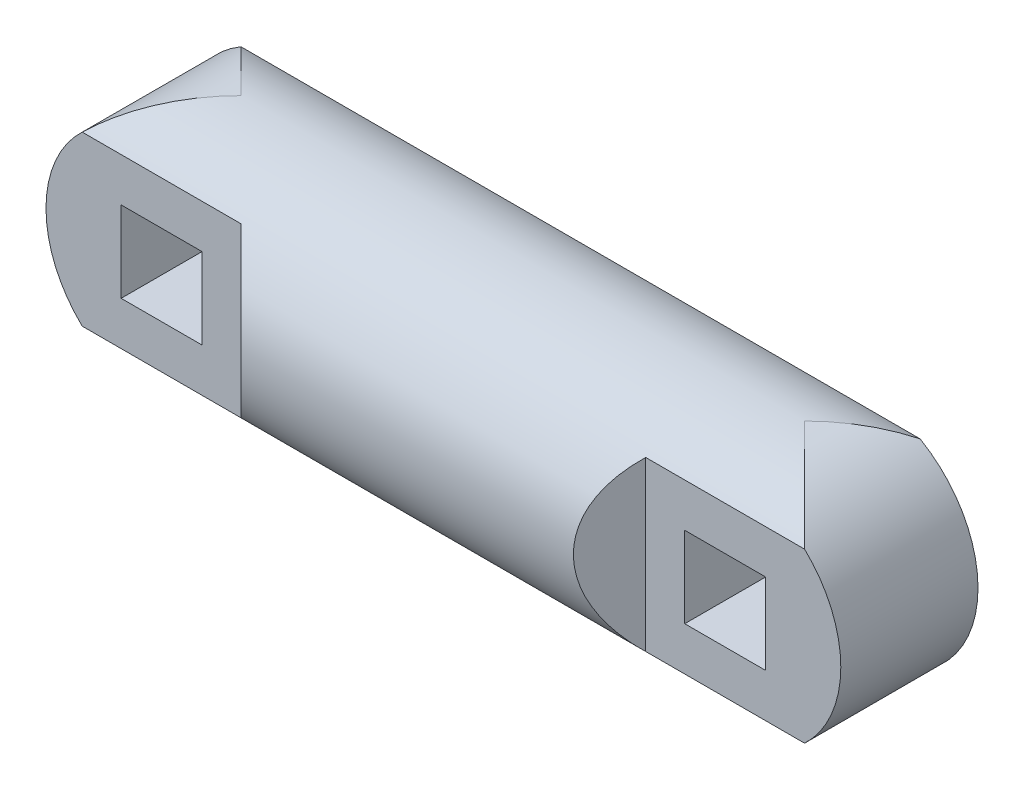
SolidWorks part; units mm, degrees
ref_plane "Plano frontal" through (0, 0, 0) normal (0, 0, 1) x (1, 0, 0)
ref_plane "Plano superior" through (0, 0, 0) normal (0, 1, 0) x (1, 0, 0)
ref_plane "Plano direito" through (0, 0, 0) normal (1, 0, 0) x (0, 0, -1)
sketch "Esboço2" plane through (0, 0, 0) normal (1, 0, 0) x (0, 0, -1)
  line L0 (-4, 0) -> (2, 0) construction
  line L1 (2, 3.4641) -> (2, -3.4641)
  arc A0 (2, 3.4641) -> (2, -3.4641) centre (0, 0) ccw
  dimension "D1" = 6
extrude "Ressalto-extrusão1" add sketch "Esboço2" along normal blind 13.75 and the other way blind 13.75
sketch "Esboço1" plane through (0, 0, 0) normal (0, 0, 1) x (1, 0, 0)
  line L0 (-9.75, 0) -> (9.75, 0) construction
  line L1 (13.75, -4) -> (13.75, 4) construction
  line L2 (8.35, 1.4) -> (11.15, 1.4)
  line L3 (8.35, 1.4) -> (8.35, -1.4)
  line L4 (8.35, -1.4) -> (11.15, -1.4)
  line L5 (11.15, 1.4) -> (11.15, -1.4)
  line L6 (8.35, 1.4) -> (11.15, -1.4) construction
  line L7 (8.35, -1.4) -> (11.15, 1.4) construction
  line L8 (9.75, 4) -> (9.75, 5)
  line L9 (9.75, 5) -> (14.75, 5)
  line L10 (14.75, 5) -> (14.75, -5)
  line L11 (9.75, -5) -> (14.75, -5)
  line L12 (9.75, -4) -> (9.75, -5)
  line L13 (0, 0) -> (0, 6.2003) construction
  line L14 (-8.35, -1.4) -> (-11.15, 1.4) construction
  line L15 (-8.35, 1.4) -> (-11.15, -1.4) construction
  line L16 (-9.75, -4) -> (-9.75, -5)
  line L17 (-9.75, -5) -> (-14.75, -5)
  line L18 (-14.75, 5) -> (-14.75, -5)
  line L19 (-9.75, 5) -> (-14.75, 5)
  line L20 (-9.75, 4) -> (-9.75, 5)
  line L21 (-11.15, 1.4) -> (-11.15, -1.4)
  line L22 (-8.35, -1.4) -> (-11.15, -1.4)
  line L23 (-8.35, 1.4) -> (-8.35, -1.4)
  line L24 (-8.35, 1.4) -> (-11.15, 1.4)
  arc A0 (9.75, -4) -> (9.75, 4) centre (9.75, 0) ccw
  arc A1 (-9.75, -4) -> (-9.75, 4) centre (-9.75, 0) cw
  point P7 (13.75, 0)
  point P17 (14.75, 0)
  point P29 (-14.75, 0)
  point P30 (-13.75, 0)
  dimension "D1" = 9.75
  dimension "D2" = 2.8
extrude "Corte-extrusão1" cut sketch "Esboço1" against normal blind 13.75 and the other way blind 13.75
sketch "Esboço3" plane through (0, 0, 0) normal (0, 1, 0) x (1, 0, 0)
  line L0 (-9.75, -3.747) -> (-9.75, 2) construction
  line L2 (-11.75, 2) -> (11.75, 2) construction
  line L3 (-9.75, 2) -> (0, 2) construction
  line L4 (0, 2) -> (0, -7.5487) construction
  line L6 (-5.75, -4.747) -> (-13.75, -2.747) construction
  line L7 (-6.7505, -2.9971) -> (-13.75, -4.747) construction
  line L8 (-7, -2.747) -> (-5.75, -4)
  line L9 (-5.75, -4.747) -> (-13.75, -4.747)
  line L10 (-5.75, -4.747) -> (-5.75, -4)
  line L11 (-7, -2.747) -> (-13.75, -2.747)
  line L12 (6.7505, -2.9971) -> (13.75, -4.747) construction
  line L13 (5.75, -4.747) -> (13.75, -2.747) construction
  line L14 (9.75, -3.747) -> (9.75, 2) construction
  line L15 (13.75, -4.747) -> (13.75, -2.747)
  line L16 (7, -2.747) -> (13.75, -2.747)
  line L17 (5.75, -4.747) -> (5.75, -4)
  line L18 (5.75, -4.747) -> (13.75, -4.747)
  line L19 (-13.75, -4.747) -> (-13.75, -2.747)
  line L20 (7, -2.747) -> (5.75, -4)
  line L21 (-8.35, -4) -> (8.35, -4) construction
extrude "Corte-extrusão2" cut sketch "Esboço3" against normal blind 13.75 and the other way blind 13.75
